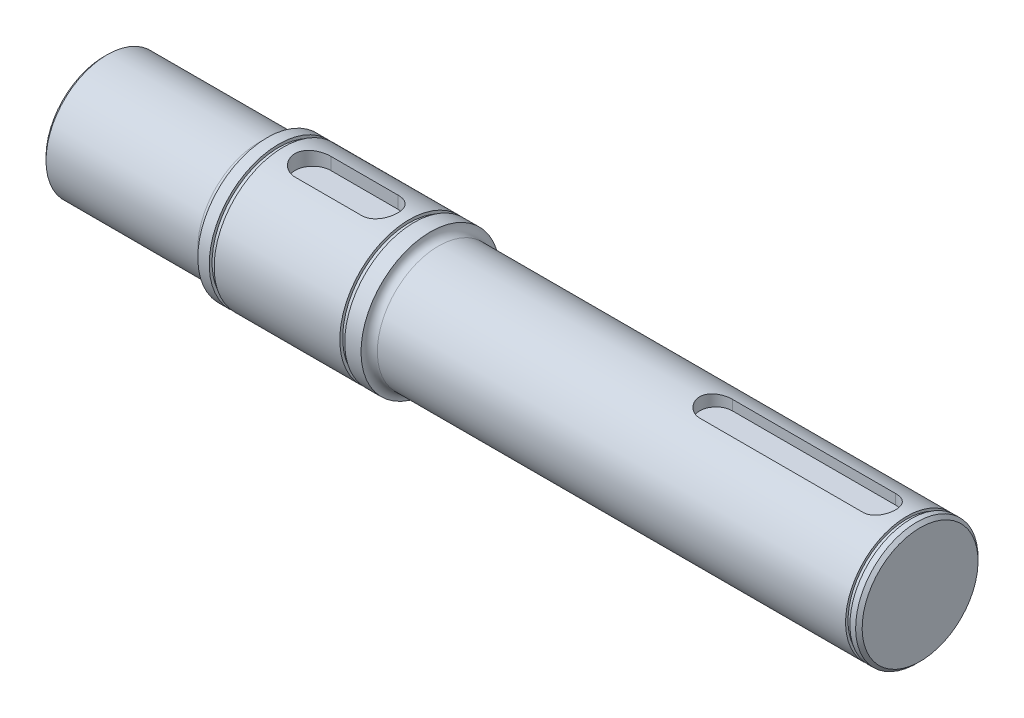
SolidWorks part; units mm, degrees
ref_plane "Front" through (0, 0, 0) normal (0, 0, 1) x (1, 0, 0)
ref_plane "Top" through (0, 0, 0) normal (0, 1, 0) x (1, 0, 0)
ref_plane "Right" through (0, 0, 0) normal (1, 0, 0) x (0, 0, -1)
sketch "Esquisse1" plane through (0, 0, 0) normal (0, 0, 1) x (1, 0, 0)
  line L0 (0, 0) -> (0, 37.5)
  line L1 (0, 37.5) -> (95, 37.5)
  line L3 (100, 42.5) -> (200, 42.5)
  line L5 (205, 37.5) -> (500, 37.5)
  line L6 (500, 37.5) -> (500, 0)
  line L7 (500, 0) -> (0, 0)
  arc A0 (100, 42.5) -> (95, 37.5) centre (95, 42.5) cw
  arc A1 (200, 42.5) -> (205, 37.5) centre (205, 42.5) ccw
  dimension "D4" = 5
  dimension "D6" = 5
  dimension "D1" = 37.5
  dimension "D2" = 100
  dimension "D3" = 500
  dimension "D5" = 42.5
  dimension "D7" = 100
revolve "Révolution1" add sketch "Esquisse1" angle 360 about L7
ref_plane "Plan1" through (110, 0, 0) normal (1, 0, 0) x (0, 0, -1)
ref_plane "Plan2" through (190, 0, 0) normal (1, 0, 0) x (0, 0, -1)
sketch "Esquisse2" plane through (110, 0, 0) normal (1, 0, 0) x (0, 0, -1)
  circle A0 centre (0, 0) radius 42.5 construction
  circle A2 centre (0, 0) radius 42.5
  circle A3 centre (0, 0) radius 40.75
  dimension "D1" = 1.75
extrude "Enlèv. mat.-Extru.1" cut sketch "Esquisse2" against normal blind 3
sketch "Esquisse3" plane through (190, 0, 0) normal (1, 0, 0) x (0, 0, -1)
  circle A0 centre (0, 0) radius 42.5 construction
  circle A1 centre (0, 0) radius 42.5
  circle A2 centre (0, 0) radius 40.75
  dimension "D1" = 1.75
extrude "Enlèv. mat.-Extru.2" cut sketch "Esquisse3" against normal blind 3
ref_plane "Plan3" through (0, 42.5, 0) normal (0, 1, 0) x (1, 0, 0)
sketch "Esquisse4" plane through (0, 42.5, 0) normal (0, 1, 0) x (1, 0, 0)
  line L0 (148.5, 42.5) -> (148.5, 0) construction
  line L1 (187, 42.5) -> (110, 42.5) construction
  line L2 (128, 0) -> (169, 0) construction
  line L3 (128, 11) -> (169, 11)
  line L4 (128, -11) -> (169, -11)
  arc A0 (128, 11) -> (128, -11) centre (128, 0) ccw
  arc A1 (169, -11) -> (169, 11) centre (169, 0) ccw
  point P6 (148.5, 0)
  dimension "D2" = 11
  dimension "D1" = 41
extrude "Enlèv. mat.-Extru.3" cut sketch "Esquisse4" against normal blind 9
ref_plane "Plan4" through (0, 37.5, 0) normal (0, 1, 0) x (1, 0, 0)
sketch "Esquisse5" plane through (0, 37.5, 0) normal (0, 1, 0) x (1, 0, 0)
  line L0 (500, 0) -> (425, 0) construction
  line L1 (500, -37.5) -> (500, 37.5) construction
  line L2 (475, 0) -> (375, 0) construction
  line L3 (475, -10) -> (375, -10)
  line L4 (475, 10) -> (375, 10)
  arc A0 (475, -10) -> (475, 10) centre (475, 0) ccw
  arc A1 (375, 10) -> (375, -10) centre (375, 0) ccw
  point P7 (425, 0)
  dimension "D2" = 10
  dimension "D1" = 75
  dimension "D3" = 100
extrude "Enlèv. mat.-Extru.4" cut sketch "Esquisse5" against normal blind 7.5
chamfer "Chanfrein1" distance 2 angle 45 2 edges at (500, 37.5, 0) (0, 37.5, 0)
ref_plane "Plan5" through (494.5, 0, 0) normal (1, 0, 0) x (0, 0, -1)
sketch "Esquisse6" plane through (494.5, 0, 0) normal (1, 0, 0) x (0, 0, -1)
  circle A0 centre (0, 0) radius 37.5 construction
  circle A1 centre (0, 0) radius 37.5
  circle A2 centre (0, 0) radius 36
  dimension "D1" = 1.5
extrude "Enlèv. mat.-Extru.5" cut sketch "Esquisse6" against normal blind 2.65
